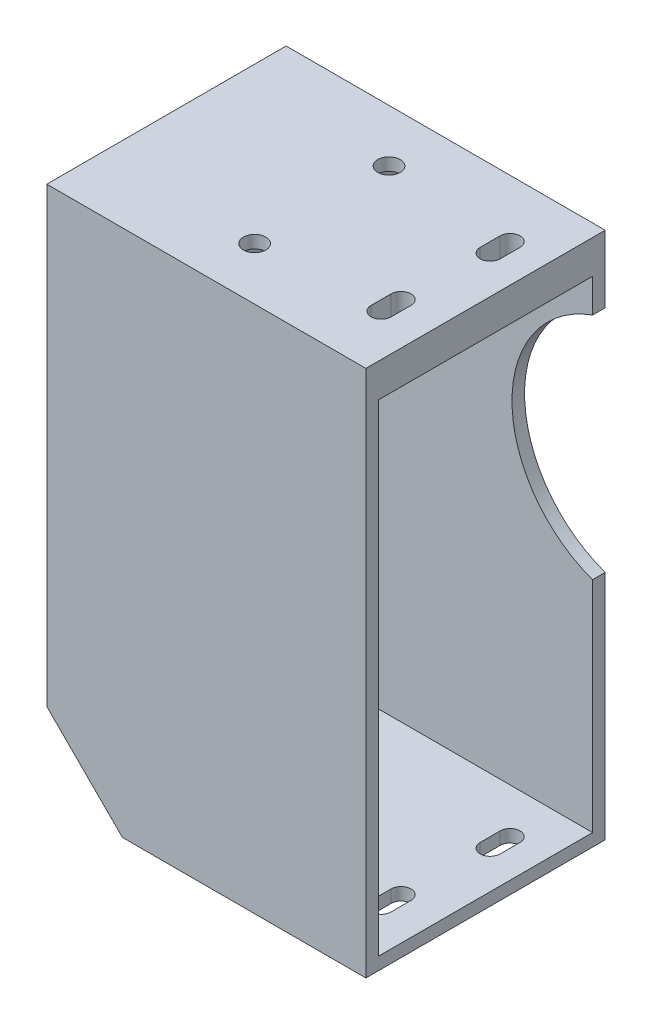
SolidWorks part; units mm, degrees
ref_plane "Front Plane" through (0, 0, 0) normal (0, 0, 1) x (1, 0, 0)
ref_plane "Top Plane" through (0, 0, 0) normal (0, 1, 0) x (1, 0, 0)
ref_plane "Right Plane" through (0, 0, 0) normal (1, 0, 0) x (0, 0, -1)
sketch "Sketch2" plane through (0, 0, 0) normal (1, 0, 0) x (0, 0, -1)
  line L0 (-22.6038, 17.8808) -> (-22.6038, -96.8692)
  line L1 (-22.6038, -96.8692) -> (28.3962, -96.8692)
  line L2 (28.3962, -96.8692) -> (28.3962, 17.8808)
  line L3 (28.3962, 17.8808) -> (-22.6038, 17.8808)
  line L4 (-25.6038, 20.8808) -> (-25.6038, -99.8692)
  line L5 (-25.6038, -99.8692) -> (31.3962, -99.8692)
  line L6 (31.3962, -99.8692) -> (31.3962, 20.8808)
  line L7 (31.3962, 20.8808) -> (-25.6038, 20.8808)
  dimension "D1" = 51
  dimension "D2" = 114.75
  dimension "D3" = 3
extrude "Boss-Extrude1" add sketch "Sketch2" along normal blind 75
sketch "Sketch3" plane through (0, 0, 0) normal (-1, 0, 0) x (0, 0, 1)
  line L0 (-31.3962, 20.8808) -> (25.6038, 20.8808)
  line L1 (25.6038, 20.8808) -> (25.6038, -99.8692)
  line L2 (25.6038, -99.8692) -> (-31.3962, -99.8692)
  line L3 (-31.3962, -99.8692) -> (-31.3962, 20.8808)
extrude "Boss-Extrude2" add sketch "Sketch3" along normal blind 3
sketch "Sketch4" plane through (0, 20.8808, 0) normal (0, 1, 0) x (1, 0, 0)
  line L0 (-3, 31.3962) -> (75, 31.3962)
  line L1 (75, 31.3962) -> (75, -25.6038)
  line L2 (75, -25.6038) -> (-3, -25.6038)
  line L3 (-3, -25.6038) -> (-3, 31.3962)
extrude "Boss-Extrude3" add sketch "Sketch4" along normal blind 5
sketch "Sketch6" plane through (0, 25.8808, 0) normal (0, 1, 0) x (1, 0, 0)
  line L0 (36, 31.3962) -> (36, -25.6038) construction
  line L1 (75, 31.3962) -> (-3, 31.3962) construction
  line L2 (-3, -25.6038) -> (75, -25.6038) construction
  line L3 (-3, 2.8962) -> (75, 2.8962) construction
  line L4 (-3, 31.3962) -> (-3, -25.6038) construction
  line L5 (75, -25.6038) -> (75, 31.3962) construction
  circle A0 centre (36, 18.8962) radius 2.675
  circle A1 centre (36, -13.1038) radius 2.675
  dimension "D1" = 5.35
  dimension "D2" = 12.5
extrude "Cut-Extrude2" cut sketch "Sketch6" against normal blind 10
sketch "Sketch8" plane through (0, 0, -31.3962) normal (0, 0, -1) x (-1, 0, 0)
  line L0 (3, -99.8692) -> (3, -79.8692)
  line L1 (3, 25.8808) -> (3, -99.8692) construction
  line L2 (3, -79.8692) -> (-17, -99.8692)
  line L3 (-75, -99.8692) -> (3, -99.8692) construction
  line L4 (-17, -99.8692) -> (3, -99.8692)
  dimension "D1" = 20
  dimension "D2" = 20
extrude "Cut-Extrude3" cut sketch "Sketch8" against normal through all
sketch "Sketch9" plane through (0, 0, 25.6038) normal (0, 0, 1) x (1, 0, 0)
  line L0 (-3, -79.8692) -> (17, -99.8692)
  line L1 (17, -99.8692) -> (21.2426, -99.8692)
  line L3 (-3, -79.8692) -> (-3, -75.6266)
  line L5 (0, -78.6266) -> (18.2426, -96.8692) construction
  line L6 (-3, -75.6266) -> (21.2426, -99.8692)
  line L8 (0, -78.6266) -> (0, -70.8578) construction
  line L9 (18.2426, -96.8692) -> (26.9937, -96.8692) construction
  line L10 (-3, -79.8692) -> (-3, -70.8578) construction
  line L11 (17, -99.8692) -> (26.9937, -99.8692) construction
  dimension "D1" = 3
extrude "Boss-Extrude4" add sketch "Sketch9" against normal up to next
sketch "Sketch15" plane through (0, -99.8692, 0) normal (0, -1, 0) x (1, 0, 0)
  line L0 (65, 9.6038) -> (66.1281, -15.3962) construction
  line L1 (62.625, 7.2288) -> (62.625, 11.9788)
  line L2 (67.375, 7.2288) -> (67.375, 11.9788)
  line L3 (63.644, -17.7276) -> (63.644, -12.9776)
  line L4 (68.394, -17.7276) -> (68.394, -12.9776)
  arc A0 (63.644, -17.7276) -> (68.394, -17.7276) centre (66.019, -17.7276) ccw
  arc A2 (62.625, 7.2288) -> (67.375, 7.2288) centre (65, 7.2288) ccw
  arc A3 (67.375, 11.9788) -> (62.625, 11.9788) centre (65, 11.9788) ccw
  arc A4 (68.394, -12.9776) -> (63.644, -12.9776) centre (66.019, -12.9776) ccw
  dimension "D1" = 2.375
  dimension "D2" = 25
  dimension "D3" = 10
  dimension "D4" = 16
  dimension "D5" = 4.75
extrude "Cut-Extrude7" cut sketch "Sketch15" against normal through all
sketch "Sketch20" plane through (0, 0, 0) normal (1, 0, 0) x (0, 0, -1)
  line L0 (-9.1038, 5.8808) -> (-9.1038, 17.8808)
  line L1 (28.3962, 17.8808) -> (-22.6038, 17.8808) construction
  line L2 (-9.1038, 17.8808) -> (14.8962, 17.8808)
  line L3 (14.8962, 17.8808) -> (14.8962, 5.8808)
  arc A0 (-9.1038, 5.8808) -> (14.8962, 5.8808) centre (2.8962, 5.8808) ccw
  dimension "D2" = 24
  dimension "D1" = 12
  dimension "D3" = 28.5
extrude "Boss-Extrude8" add sketch "Sketch20" along normal blind 5
sketch "Sketch21" plane through (5, 0, 0) normal (1, 0, 0) x (0, 0, -1)
  line L0 (2.8962, -79.8692) -> (2.8962, 25.8808) construction
  line L1 (-25.6038, -79.8692) -> (31.3962, -79.8692) construction
  line L2 (31.3962, 25.8808) -> (-25.6038, 25.8808) construction
  circle A0 centre (2.8962, 5.9373) radius 3
  dimension "D1" = 6
extrude "Cut-Extrude11" cut sketch "Sketch21" against normal blind 1094
chamfer "Chamfer2" distance 2 angle 73.5 1 edges at (5, 5.9373, -5.8962) first distance on face at (5, 5.9373, -5.8962)
sketch "Sketch22" plane through (5, 0, 0) normal (1, 0, 0) x (0, 0, -1)
  line L0 (-9.1038, 5.8808) -> (14.8962, 5.8808) construction
  line L1 (2.8962, 25.8808) -> (2.8962, -79.8692) construction
  line L2 (31.3962, 25.8808) -> (-25.6038, 25.8808) construction
  line L3 (-25.6038, -79.8692) -> (31.3962, -79.8692) construction
  circle A0 centre (-5.6038, 5.8808) radius 1.675
  circle A1 centre (11.3962, 5.8808) radius 1.675
  dimension "D1" = 3.35
  dimension "D2" = 17
  dimension "D3" = 8.5
extrude "Cut-Extrude12" cut sketch "Sketch22" against normal blind 1094
sketch "Sketch24" plane through (0, 17.8808, 0) normal (0, -1, 0) x (1, 0, 0)
  line L0 (75, -2.8962) -> (5, -2.8962) construction
  line L1 (75, -28.3962) -> (75, 22.6038) construction
  line L2 (5, -14.8962) -> (5, 9.1038) construction
  line L4 (40.8209, -18.8962) -> (38.4104, -14.7212)
  line L5 (38.4104, -14.7212) -> (33.5896, -14.7212)
  line L6 (33.5896, -14.7212) -> (31.1791, -18.8962)
  line L7 (31.1791, -18.8962) -> (33.5896, -23.0712)
  line L8 (33.5896, -23.0712) -> (38.4104, -23.0712)
  line L9 (38.4104, -23.0712) -> (40.8209, -18.8962)
  line L11 (38.4104, 17.2788) -> (40.8209, 13.1038)
  line L12 (33.5896, 17.2788) -> (38.4104, 17.2788)
  line L13 (31.1791, 13.1038) -> (33.5896, 17.2788)
  line L14 (33.5896, 8.9288) -> (31.1791, 13.1038)
  line L15 (38.4104, 8.9288) -> (33.5896, 8.9288)
  line L16 (40.8209, 13.1038) -> (38.4104, 8.9288)
  line L17 (33.5896, -23.0712) -> (38.4104, -23.0712) [skipped]
  circle A0 centre (36, -18.8962) radius 4.175 construction
  circle A1 centre (36, 13.1038) radius 4.175 construction
  dimension "D1" = 8.35
extrude "Cut-Extrude13" cut sketch "Sketch24" against normal blind 5
sketch "Sketch25" plane through (-3, 0, 0) normal (-1, 0, 0) x (0, 0, 1)
  line L0 (-2.8962, 25.8808) -> (-2.8962, -79.8692) construction
  line L1 (-31.3962, 25.8808) -> (25.6038, 25.8808) construction
  line L2 (25.6038, -79.8692) -> (-31.3962, -79.8692) construction
  circle A0 centre (-2.8962, -26.9942) radius 5.125
  dimension "D1" = 10.25
extrude "Cut-Extrude14" cut sketch "Sketch25" against normal through all
chamfer "Chamfer3" distance 2 angle 45 3 edges at (-3, -26.9942, -31.3962) (-3, 25.8808, -2.8962) (-3, -26.9942, 25.6038)
fillet "Fillet1" radius 2 1 edges at (-3, 5.9373, -5.8962)
sketch "Sketch27" plane through (-3, 0, 0) normal (-1, 0, 0) x (0, 0, 1)
  circle A0 centre (-11.3962, 5.8808) radius 3
  circle A1 centre (5.6038, 5.8808) radius 3
  dimension "D1" = 6
  dimension "D2" = 6
extrude "Cut-Extrude15" cut sketch "Sketch27" against normal blind 3
sketch "Sketch28" plane through (0, 0, -31.3962) normal (0, 0, -1) x (-1, 0, 0)
  line L0 (-75, 9.8808) -> (-75, -44.7072)
  arc A1 (-75, -44.7072) -> (-75, 9.8808) centre (-84.8, -17.4132) ccw
  dimension "D1" = 29
  dimension "D2" = 16
  dimension "D3" = 9.8
extrude "Cut-Extrude16" cut sketch "Sketch28" against normal blind 10
